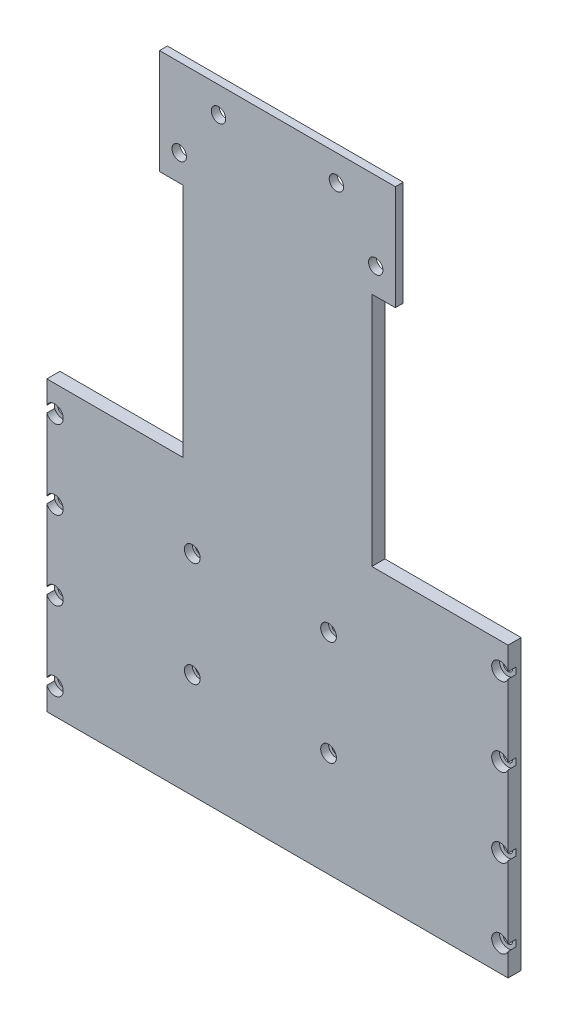
SolidWorks part; units mm, degrees
ref_plane "正面" through (0, 0, 0) normal (0, 0, 1) x (1, 0, 0)
ref_plane "平面" through (0, 0, 0) normal (0, 1, 0) x (1, 0, 0)
ref_plane "右側面" through (0, 0, 0) normal (1, 0, 0) x (0, 0, -1)
sketch "ｽｹｯﾁ1" plane through (0, 0, 0) normal (0, 0, 1) x (1, 0, 0)
  line L0 (-45, -20) -> (-36, -20)
  line L2 (-45, -20) -> (-45, 20)
  line L3 (-45, 20) -> (45, 20)
  line L4 (45, -20) -> (45, 20)
  line L5 (-45, -20) -> (45, 20) construction
  line L6 (-45, 20) -> (45, -20) construction
  line L7 (-36, -20) -> (-36, -220)
  line L8 (-36, -220) -> (36, -220)
  line L9 (36, -220) -> (36, -20)
  line L10 (36, -20) -> (45, -20)
  point P0 (0, 0)
  dimension "D1" = 40
  dimension "D2" = 90
  dimension "D3" = 9
  dimension "D4" = 72
  dimension "D5" = 200
extrude "ﾎﾞｽ - 押し出し1" add sketch "ｽｹｯﾁ1" along normal blind 3
sketch "ｽｹｯﾁ2" plane through (0, 0, 0) normal (0, 0, -1) x (-1, 0, 0)
  line L1 (-36, -20) -> (36, -20)
  line L2 (-36, -20) -> (-36, -220)
  line L3 (-36, -220) -> (36, -220)
  line L4 (36, -20) -> (36, -220)
extrude "ﾎﾞｽ - 押し出し2" add sketch "ｽｹｯﾁ2" along normal blind 2
sketch "ｽｹｯﾁ4" plane through (0, 0, 0) normal (0, 0, -1) x (-1, 0, 0)
  line L0 (-45, -20) -> (-45, 20) construction
  line L1 (45, 20) -> (45, -20) construction
  line L2 (-45, 20) -> (45, 20) construction
  line L3 (-36, -20) -> (-45, -20) construction
  line L4 (45, -20) -> (36, -20) construction
  circle A0 centre (-22.5, 10) radius 2.75
  circle A1 centre (22.5, 10) radius 2.75
  circle A2 centre (37.5, -10) radius 2.75
  circle A3 centre (-37.5, -10) radius 2.75
  dimension "D1" = 5.5
  dimension "D2" = 5.5
  dimension "D3" = 5.5
  dimension "D4" = 5.5
  dimension "D5" = 25
  dimension "D6" = 7.5
  dimension "D7" = 45
  dimension "D8" = 7.5
  dimension "D9" = 10
  dimension "D10" = 10
  dimension "D11" = 10
  dimension "D12" = 10
extrude "ｶｯﾄ - 押し出し1" cut sketch "ｽｹｯﾁ4" against normal through all
sketch "ｽｹｯﾁ7" plane through (0, 0, 3) normal (0, 0, 1) x (1, 0, 0)
  line L1 (36, -220) -> (88, -220)
  line L2 (36, -220) -> (36, -110)
  line L3 (36, -110) -> (88, -110)
  line L4 (88, -220) -> (88, -110)
  dimension "D1" = 52
  dimension "D2" = 110
extrude "ﾎﾞｽ - 押し出し3" add sketch "ｽｹｯﾁ7" against normal up to surface (5 mm away) up to face at (0, -120, -2)
sketch "ｽｹｯﾁ8" plane through (0, 0, 3) normal (0, 0, 1) x (1, 0, 0)
  line L0 (-36, -220) -> (88, -220) construction
  line L1 (88, -220) -> (88, -110) construction
  line L2 (88, -220) -> (88, -110) construction
  circle A0 centre (85, -180) radius 1.75
  circle A1 centre (85, -210) radius 1.75
  circle A2 centre (85, -150) radius 1.75
  circle A3 centre (85, -120) radius 1.75
  dimension "D1" = 3.5
  dimension "D2" = 3.5
  dimension "D7" = 3.5
  dimension "D10" = 3.5
  dimension "D3" = 10
  dimension "D4" = 30
  dimension "D5" = 3
  dimension "D6" = 3
  dimension "D8" = 3
  dimension "D9" = 30
  dimension "D11" = 3
  dimension "D12" = 30
extrude "ｶｯﾄ - 押し出し2" cut sketch "ｽｹｯﾁ8" against normal through all
sketch "ｽｹｯﾁ9" plane through (0, 0, 3) normal (0, 0, 1) x (1, 0, 0)
  circle A0 centre (85, -180) radius 3.25
  circle A1 centre (85, -210) radius 3.25
  circle A2 centre (85, -150) radius 3.25
  circle A3 centre (85, -120) radius 3.25
  dimension "D1" = 6.5
  dimension "D2" = 6.5
  dimension "D3" = 6.5
  dimension "D4" = 6.5
extrude "ｶｯﾄ - 押し出し3" cut sketch "ｽｹｯﾁ9" against normal blind 3
mirror "ﾐﾗｰ1" about plane through (0, 0, 0) normal (1, 0, 0) of "ｶｯﾄ - 押し出し1", "ｶｯﾄ - 押し出し2", "ｶｯﾄ - 押し出し3", "ﾎﾞｽ - 押し出し3", "ﾎﾞｽ - 押し出し1"
ref_axis "軸1" through (0, -200.5, 0) along (0, 1, 0)
sketch "ｽｹｯﾁ10" plane through (0, 0, 3) normal (0, 0, 1) x (1, 0, 0)
  line L0 (88, -110) -> (36, -110) construction
  line L1 (-88, -110) -> (-36, -110) construction
  line L2 (0, -200.5) -> (0, 30.5) construction
  circle A0 centre (19.5, -140) radius 1.75
  circle A1 centre (19.5, -180) radius 1.75
  circle A2 centre (-32.5, -180) radius 1.75
  circle A3 centre (-32.5, -140) radius 1.75
  dimension "D1" = 3.5
  dimension "D2" = 3.5
  dimension "D3" = 3.5
  dimension "D4" = 3.5
  dimension "D5" = 40
  dimension "D6" = 30
  dimension "D7" = 30
  dimension "D8" = 40
  dimension "D9" = 52
  dimension "D10" = 52
  dimension "D11" = 32.5
  dimension "D12" = 32.5
extrude "ｶｯﾄ - 押し出し4" cut sketch "ｽｹｯﾁ10" against normal through all
sketch "ｽｹｯﾁ11" plane through (0, 0, 3) normal (0, 0, 1) x (1, 0, 0)
  circle A0 centre (-32.5, -140) radius 3
  circle A1 centre (19.5, -140) radius 3
  circle A2 centre (19.5, -180) radius 3
  circle A3 centre (-32.5, -180) radius 3
  dimension "D1" = 6
  dimension "D2" = 6
  dimension "D3" = 6
  dimension "D4" = 6
extrude "ｶｯﾄ - 押し出し5" cut sketch "ｽｹｯﾁ11" against normal blind 3
